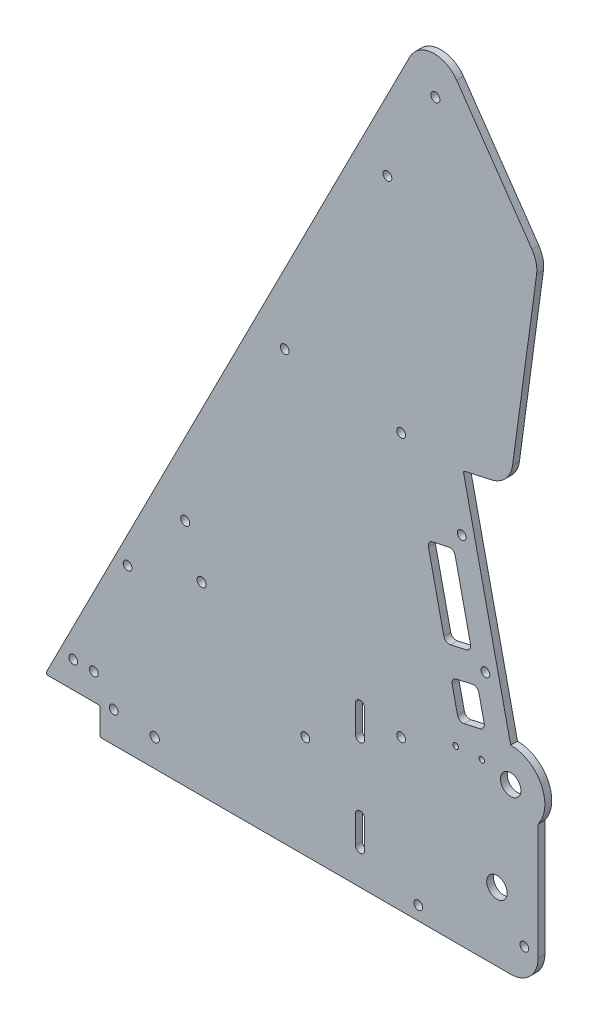
SolidWorks part; units mm, degrees
other "Markup1"
sketch "Sketch5"
ref_plane "Front Plane" through (0, 0, 0) normal (0, 0, 1) x (1, 0, 0)
ref_plane "Top Plane" through (0, 0, 0) normal (0, 1, 0) x (1, 0, 0)
ref_plane "Right Plane" through (0, 0, 0) normal (1, 0, 0) x (0, 0, -1)
sketch "Sketch1" plane through (0, 0, 0) normal (0, 0, 1) x (1, 0, 0)
  line L1 (228.6, -12.7) -> (228.6, 53.975)
  line L2 (178.7547, 351.4131) -> (0, 0)
  line L3 (228.6, 279.4) -> (178.7547, 351.4131)
  line L5 (0, 0) -> (25.4, 0)
  line L6 (25.4, 0) -> (25.4, -12.7)
  line L7 (25.4, -12.7) -> (228.6, -12.7)
  line L9 (215.9, 79.375) -> (193.9097, 178.5667)
  line L10 (193.9097, 178.5667) -> (215.6079, 183.377)
  line L11 (215.6079, 183.377) -> (228.6, 279.4)
  arc A0 (228.6, 53.975) -> (215.9, 79.375) centre (215.9, 63.5) ccw
  dimension "D7" = 12.7
  dimension "D8" = 76.2
  dimension "D10" = 31.75
  dimension "D2" = 292.1
  dimension "D3" = 25.4
  dimension "D4" = 215.9
  dimension "D5" = 394.2644
  dimension "D6" = 203.2
  dimension "D9" = 63.039
  dimension "D11" = 101.6
  dimension "D12" = 12.5
  dimension "D13" = 22.225
extrude "Boss-Extrude1" add sketch "Sketch1" along normal blind 3.175
sketch "Sketch2" plane through (0, 0, 3.175) normal (0, 0, 1) x (1, 0, 0)
  line L0 (178.7547, 351.4131) -> (0, 0) construction
  line L1 (25.4, -12.7) -> (228.6, -12.7) construction
  line L2 (215.9, 79.375) -> (193.9097, 178.5667) construction
  line L3 (193.9097, 178.5667) -> (215.6079, 183.377) construction
  line L4 (215.9, 79.375) -> (193.9097, 178.5667) construction
  line L5 (64.9432, 94.0578) -> (72.5445, 73.1732) construction
  line L6 (64.9432, 94.0578) -> (89.8317, 94.0578) construction
  line L10 (228.6, -12.7) -> (228.6, 53.975) construction
  circle A0 centre (64.9432, 94.0578) radius 2.0955
  circle A1 centre (180.975, 322.1643) radius 2.0955
  circle A2 centre (72.5445, 73.1732) radius 2.0955
  circle A3 centre (193.2078, 152.3944) radius 2.032
  circle A4 centre (215.9, 63.5) radius 4.7625
  circle A7 centre (173.0375, -6.35) radius 2.032
  circle A8 centre (204.203, 102.7985) radius 2.032
  circle A26 centre (209.55, 19.05) radius 4.7625
  arc A30 (228.6, 53.975) -> (215.9, 79.375) centre (215.9, 63.5) ccw construction
  circle A31 centre (165.1, 179.3875) radius 2.032
  dimension "D3" = 4.191
  dimension "D5" = 4.191
  dimension "D9" = 4.191
  dimension "D20" = 9.525
  dimension "D23" = 9.525
  dimension "D18" = 4.064
  dimension "D26" = 4.064
  dimension "D14" = 4.064
  dimension "D2" = 15.24
  dimension "D6" = 15.24
  dimension "D7" = 22.225
  dimension "D21" = 44.45
  dimension "D22" = 6.35
  dimension "D19" = 160.3375
  dimension "D24" = 44.45
  dimension "D25" = 6.35
  dimension "D27" = 25.4
  dimension "D28" = 50.8
  dimension "D29" = 6.35
  dimension "D17" = 6.35
  dimension "D33" = 55.5625
  dimension "D15" = 114.3
  dimension "D4" = 180.975
  dimension "D8" = 70
extrude "Cut-Extrude1" cut sketch "Sketch2" against normal through all
sketch "Sketch7" plane through (0, 0, 3.175) normal (0, 0, 1) x (1, 0, 0)
  line L0 (146.05, 3.175) -> (146.05, 15.875) construction
  line L1 (143.891, 3.175) -> (143.891, 15.875)
  line L2 (148.209, 3.175) -> (148.209, 15.875)
  line L3 (146.05, 47.625) -> (146.05, 60.325) construction
  line L4 (143.891, 47.625) -> (143.891, 60.325)
  line L5 (148.209, 47.625) -> (148.209, 60.325)
  line L6 (25.4, -12.7) -> (228.6, -12.7) construction
  line L12 (228.6, -12.7) -> (228.6, 53.975) construction
  line L13 (25.4, -12.7) -> (228.6, -12.7) construction
  arc A0 (143.891, 3.175) -> (148.209, 3.175) centre (146.05, 3.175) ccw
  arc A1 (148.209, 15.875) -> (143.891, 15.875) centre (146.05, 15.875) ccw
  arc A2 (143.891, 47.625) -> (148.209, 47.625) centre (146.05, 47.625) ccw
  arc A3 (148.209, 60.325) -> (143.891, 60.325) centre (146.05, 60.325) ccw
  circle A8 centre (50.8, 0) radius 2.159
  point P2 (146.05, 9.525)
  point P9 (146.05, 53.975)
  dimension "D1" = 4.318
  dimension "D5" = 4.318
  dimension "D2" = 12.7
  dimension "D3" = 12.7
  dimension "D4" = 44.45
  dimension "D6" = 95.25
  dimension "D7" = 82.55
  dimension "D8" = 15.875
  dimension "D9" = 12.7
extrude "Cut-Extrude2" cut sketch "Sketch7" against normal through all
sketch "Sketch10" plane through (0, 0, 3.175) normal (0, 0, 1) x (1, 0, 0)
  circle A1 centre (165.1, 57.15) radius 2.032
  circle A2 centre (120.65, 34.925) radius 2.032
  circle A3 centre (13.0465, 12.3347) radius 2.032
  circle A4 centre (22.5715, 12.3347) radius 2.032
  circle A5 centre (38.2114, 62.6398) radius 2.032
  dimension "D1" = 4.064
  dimension "D2" = 4.064
  dimension "D4" = 63.5
  dimension "D5" = 69.85
extrude "Cut-Extrude3" cut sketch "Sketch10" against normal up to next
fillet "Fillet1" radius 12.7 4 edges at (228.6, -12.7, 1.5875) (178.7547, 351.4131, 1.5875) (215.6079, 183.377, 1.5875) (228.6, 279.4, 1.5875)
fillet "Fillet2" radius 0.7937 4 edges at (25.4, -12.7, 1.5875) (25.4, 0, 1.5875) (193.9097, 178.5667, 1.5875) (0, 0, 1.5875)
sketch "Sketch12" plane through (0, 0, 3.175) normal (0, 0, 1) x (1, 0, 0)
  circle A0 centre (31.75, 1.5875) radius 2.032
  circle A1 centre (222.25, 1.5875) radius 2.032
  dimension "D1" = 4.064
extrude "Cut-Extrude5" cut sketch "Sketch12" against normal through all
sketch "Sketch13" plane through (0, 0, 3.175) normal (0, 0, 1) x (1, 0, 0)
  line L0 (189.6226, 145.0954) -> (197.869, 107.8985)
  line L1 (177.2237, 142.3466) -> (185.47, 105.1497)
  line L2 (215.9, 79.375) -> (194.0815, 177.7917) construction
  line L3 (185.47, 105.1497) -> (197.869, 107.8985)
  line L4 (177.2237, 142.3466) -> (189.6226, 145.0954)
  line L5 (194.6847, 178.7385) -> (206.9592, 181.4597) construction
  line L6 (190.4268, 66.2609) -> (202.5335, 66.7895) construction
  line L7 (188.2188, 92.7508) -> (200.6178, 95.4995)
  line L8 (188.2188, 92.7508) -> (191.7922, 76.6321)
  line L9 (191.7922, 76.6321) -> (204.1912, 79.3809)
  line L10 (200.6178, 95.4995) -> (204.1912, 79.3809)
  line L11 (190.4268, 66.2609) -> (191.7922, 76.6321) construction
  line L12 (202.5335, 66.7895) -> (204.1912, 79.3809) construction
  circle A0 centre (190.4268, 66.2609) radius 1.27
  circle A1 centre (202.5335, 66.7895) radius 1.27
  point P3 (193.7458, 126.4969)
  point P6 (181.3468, 123.7481)
  dimension "D7" = 2.54
  dimension "D1" = 38.1
  dimension "D2" = 12.7
  dimension "D3" = 11.43
  dimension "D4" = 50.8
  dimension "D5" = 16.51
  dimension "D6" = 12.7
  dimension "D8" = 110
  dimension "D9" = 80
  dimension "D10" = 12.7
extrude "Cut-Extrude6" cut sketch "Sketch13" against normal through all both and the other way through all
sketch "Sketch14" plane through (0, 0, 3.175) normal (0, 0, 1) x (1, 0, 0)
  line L0 (26.1937, -12.7) -> (215.9, -12.7) construction
  line L1 (228.6, 0) -> (228.6, 53.975) construction
  circle A0 centre (158.75, 279.4) radius 2.032
  circle A1 centre (111.125, 186.055) radius 2.032
  dimension "D1" = 4.064
  dimension "D2" = 198.755
  dimension "D3" = 117.475
  dimension "D4" = 69.85
  dimension "D5" = 292.1
extrude "Cut-Extrude7" cut sketch "Sketch14" against normal up to next
fillet "Fillet3" radius 2.54 8 edges at (177.2237, 142.3466, 1.5875) (189.6226, 145.0954, 1.5875) (197.869, 107.8985, 1.5875) (185.47, 105.1497, 1.5875) (200.6178, 95.4995, 1.5875) (188.2188, 92.7508, 1.5875) (191.7922, 76.6321, 1.5875) (204.1912, 79.3809, 1.5875)
equation "\"D6@Sketch2\"=\"D2@Sketch2\""
